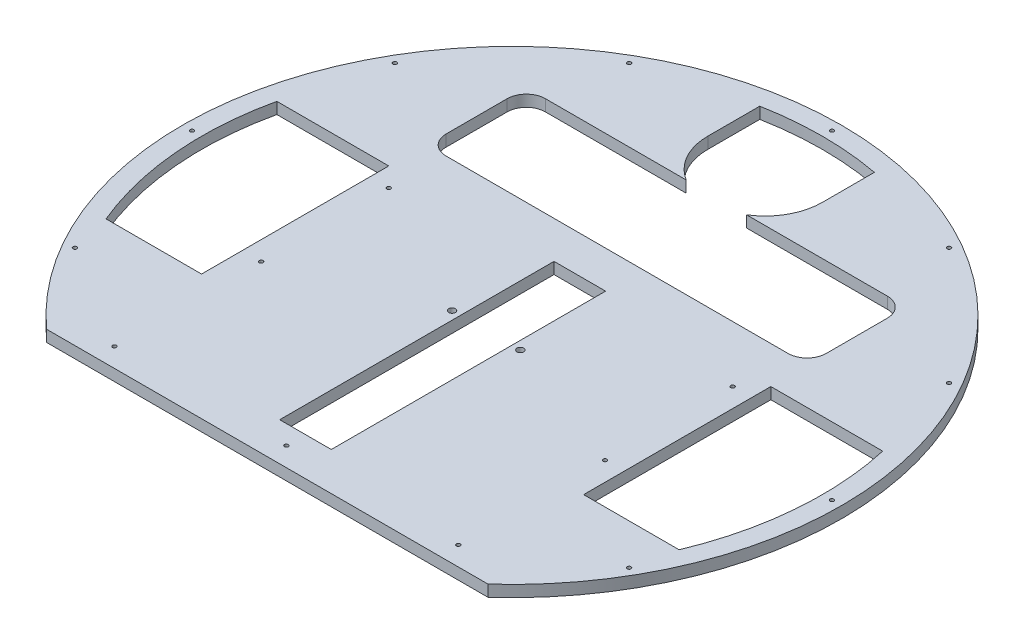
SolidWorks part; units mm, degrees
ref_plane "Front Plane" through (0, 0, 0) normal (0, 0, 1) x (1, 0, 0)
ref_plane "Top Plane" through (0, 0, 0) normal (0, 1, 0) x (1, 0, 0)
ref_plane "Right Plane" through (0, 0, 0) normal (1, 0, 0) x (0, 0, -1)
sketch "Sketch1" plane through (0, 0, 0) normal (0, 1, 0) x (1, 0, 0)
  line L0 (0, 0) -> (0, -162.5) construction
  line L2 (-100, -144.5) -> (100, -144.5)
  line L3 (-100, -144.5) -> (-100, 35.5)
  line L4 (-100, 35.5) -> (100, 35.5)
  line L5 (100, -144.5) -> (100, 35.5)
  line L6 (-100, -144.5) -> (100, 35.5) construction
  line L7 (-100, 35.5) -> (100, -144.5) construction
  circle A0 centre (0, 0) radius 162.5
  point P4 (0, -54.5)
  dimension "D1" = 325
  dimension "D2" = 180
  dimension "D3" = 35.5
  dimension "D4" = 200
sketch "Sketch2" plane through (0, 0, 0) normal (0, 1, 0) x (1, 0, 0)
  line L0 (-100, -144.5) -> (-100, 35.5) construction
  line L1 (-100, 35.5) -> (100, 35.5) construction
  line L2 (100, -144.5) -> (100, 35.5) construction
  line L3 (-100, -128.0869) -> (-100, 35.5)
  line L4 (-100, 35.5) -> (100, 35.5)
  line L5 (100, -128.0869) -> (100, 35.5)
  circle A0 centre (0, 0) radius 162.5 construction
  arc A1 (100, -128.0869) -> (-100, -128.0869) centre (0, 0) ccw
extrude "Boss-Extrude1" add sketch "Sketch2" along normal blind 6
sketch "Sketch4" plane through (0, 6, 0) normal (0, 1, 0) x (1, 0, 0)
  line L0 (0, 0) -> (0, 162.5) construction
  line L1 (119.15, -101.1581) -> (123.8764, -105.1708) construction
  line L2 (100, 35.5) -> (100, -128.0869) construction
  line L4 (-100, 35.5) -> (100, 35.5) construction
  arc A0 (100, -128.0869) -> (-100, -128.0869) centre (0, 0) ccw construction
  circle A1 centre (119.15, -101.1581) radius 1
  circle A2 centre (87.75, 86.5) radius 1
  circle A3 centre (152, 23.5891) radius 1
  circle A4 centre (-87.75, 86.5) radius 1
  circle A5 centre (99, 36.6) radius 1
  circle A6 centre (-99, 36.6) radius 1
  circle A7 centre (-152, 23.5891) radius 1
  circle A8 centre (-119.15, -101.1581) radius 1
  dimension "D1" = 2
  dimension "D3" = 6.2
  dimension "D2" = 129
  dimension "D4" = 19.15
  dimension "D5" = 52
  dimension "D6" = 51
  dimension "D7" = 87.75
  dimension "D8" = 1.1
extrude "Cut-Extrude2" [suppressed] cut sketch "Sketch4" against normal through all
sketch "Sketch5" plane through (0, 6, 0) normal (0, 1, 0) x (1, 0, 0)
  line L0 (-100, -128.0869) -> (-100, 35.5) construction
  line L1 (-100, -108.0869) -> (100, -108.0869)
  line L2 (-100, -108.0869) -> (-100, -128.0869)
  line L3 (-100, -128.0869) -> (100, -128.0869)
  line L4 (100, -108.0869) -> (100, -128.0869)
  dimension "D1" = 20
extrude "Boss-Extrude2" add sketch "Sketch5" against normal blind 6
sketch "Sketch6" plane through (0, 6, 0) normal (0, 1, 0) x (1, 0, 0)
  line L0 (0, 0) -> (0, -108.0869) construction
  line L1 (100, -108.0869) -> (-100, -108.0869) construction
  line L2 (-100, 35.5) -> (100, 35.5) construction
  line L4 (-13.5, -108.0869) -> (-13.5, 35.5)
  line L5 (-13.5, -108.0869) -> (-100, -108.0869)
  line L6 (13.5, -108.0869) -> (13.5, 35.5)
  line L7 (-13.5, -108.0869) -> (13.5, 35.5) construction
  line L8 (-13.5, 35.5) -> (13.5, -108.0869) construction
  line L9 (-100, -108.0869) -> (-100, 35.5) construction
  line L10 (-100, -108.0869) -> (-100, 35.5)
  line L11 (100, -108.0869) -> (13.5, -108.0869)
  line L12 (-13.5, 35.5) -> (-100, 35.5)
  line L13 (-100, -108.0869) -> (100, -108.0869)
  line L14 (-100, 35.5) -> (-100, -108.0869)
  line L15 (100, 35.5) -> (-100, 35.5)
  line L16 (100, -108.0869) -> (100, 35.5)
  line L17 (-100, -108.0869) -> (-13.5, -108.0869)
  line L18 (-100, 35.5) -> (-100, -108.0869)
  line L19 (100, 35.5) -> (13.5, 35.5)
  line L20 (100, -108.0869) -> (100, 35.5)
  line L21 (13.5, -108.0869) -> (100, -108.0869)
  point P5 (0, -36.2934)
  line M5 (100, -108.0869) -> (-100, -108.0869)
  line M6 (-100, -108.0869) -> (-100, 35.5)
  line M7 (-100, 35.5) -> (100, 35.5)
  line M8 (100, 35.5) -> (100, -108.0869)
  dimension "D1" = 27
  dimension "D2" = 0
extrude "Boss-Extrude3" add sketch "Sketch6" against normal through all contours L4 M5 M7 M6 | L6 M5 M8 M7 region at (-56.75, 6, 36.2934) region at (56.75, 6, 36.2934)
sketch "Sketch7" plane through (0, 6, 0) normal (0, 1, 0) x (1, 0, 0)
  line L0 (-150, -62.5) -> (-100, -62.5)
  line L1 (-100, -144.5) -> (-100, 35.5) construction
  line L2 (-158.5749, 35.5) -> (-100, 35.5)
  line L3 (-100, 35.5) -> (-100, -62.5)
  line L4 (0, 0) -> (0, -162.5) construction
  line L5 (100, 35.5) -> (100, -62.5)
  line L6 (158.5749, 35.5) -> (100, 35.5)
  line L7 (150, -62.5) -> (100, -62.5)
  line L8 (-100, 35.5) -> (100, 35.5) construction
  arc A0 (100, -128.0869) -> (-100, -128.0869) centre (0, 0) ccw construction
  circle A1 centre (0, 0) radius 162.5 construction
  arc A2 (-158.5749, 35.5) -> (-150, -62.5) centre (0, 0) ccw
  arc A3 (158.5749, 35.5) -> (150, -62.5) centre (0, 0) cw
  dimension "D1" = 50
extrude "Cut-Extrude3" cut sketch "Sketch7" against normal through all
sketch "Sketch8" plane through (0, 6, 0) normal (0, 1, 0) x (1, 0, 0)
  line L0 (0, 162.5) -> (0, 0) construction
  line L1 (-30, 132.5) -> (-30, 159.7068)
  line L2 (30, 132.5) -> (30, 159.7068)
  arc A0 (-30, 132.5) -> (30, 132.5) centre (0, 132.5) ccw
  circle A1 centre (0, 0) radius 162.5 construction
  arc A2 (30, 159.7068) -> (-30, 159.7068) centre (0, 0) ccw
  dimension "D1" = 60
extrude "Cut-Extrude4" cut sketch "Sketch8" against normal through all
sketch "Sketch9" plane through (0, 6, 0) normal (0, 1, 0) x (1, 0, 0)
  line L0 (0, 0) -> (0, 162.5) construction
  line L1 (-99.5, 107) -> (99.5, 107)
  line L2 (-99.5, 107) -> (-99.5, 55)
  line L3 (-99.5, 55) -> (99.5, 55)
  line L4 (99.5, 107) -> (99.5, 55)
  line L5 (-99.5, 107) -> (99.5, 55) construction
  line L6 (-99.5, 55) -> (99.5, 107) construction
  line L7 (-100, 35.5) -> (100, 35.5) construction
  circle A0 centre (0, 0) radius 162.5 construction
  point P0 (0, 81)
  dimension "D1" = 52
  dimension "D2" = 199
  dimension "D3" = 19.5
extrude "Cut-Extrude5" cut sketch "Sketch9" against normal through all
sketch "Sketch10" plane through (0, 6, 0) normal (0, 1, 0) x (1, 0, 0)
  line L0 (-100, -128.0869) -> (-115.5422, -128.0869)
  line L1 (100, -128.0869) -> (115.5422, -128.0869)
  arc A0 (115.5422, -128.0869) -> (-115.5422, -128.0869) centre (0, 0) ccw
  circle A1 centre (0, 0) radius 162.5 construction
  arc A2 (100, -128.0869) -> (-100, -128.0869) centre (0, 0) ccw
  dimension "D1" = 10
extrude "Boss-Extrude4" add sketch "Sketch10" against normal through all
fillet "Fillet1" radius 10 4 edges at (99.5, 3, -107) (99.5, 3, -55) (-99.5, 3, -55) (-99.5, 3, -107)
sketch "Sketch11" plane through (0, 6, 0) normal (0, 1, 0) x (1, 0, 0)
  line L0 (0, 172.5) -> (0, 162.5) construction
  arc A1 (115.5422, -128.0869) -> (-115.5422, -128.0869) centre (0, 0) ccw construction
  arc A2 (30, 159.7068) -> (-30, 159.7068) centre (0, 0) ccw construction
  circle A3 centre (0, 167.5) radius 1
  circle A4 centre (83.75, 145.0593) radius 1
  circle A5 centre (145.0593, 83.75) radius 1
  circle A6 centre (167.5, 0) radius 1
  circle A7 centre (145.0593, -83.75) radius 1
  circle A8 centre (83.75, -145.0593) radius 1
  circle A9 centre (0, -167.5) radius 1
  circle A10 centre (-83.75, -145.0593) radius 1
  circle A11 centre (-145.0593, -83.75) radius 1
  circle A12 centre (-167.5, 0) radius 1
  circle A13 centre (-145.0593, 83.75) radius 1
  circle A14 centre (-83.75, 145.0593) radius 1
  point P36 (0, 0)
  dimension "D1" = 2
  dimension "D2" = 12
extrude "Cut-Extrude6" cut sketch "Sketch11" against normal through all
sketch "Sketch12" plane through (0, 6, 0) normal (0, 1, 0) x (1, 0, 0)
  line L0 (-125.7447, -118.0869) -> (125.7447, -118.0869) construction
  line L1 (-115.5422, -128.0869) -> (115.5422, -128.0869) construction
  line L2 (-100, -144.5) -> (-100, 35.5) construction
  line L3 (100, -144.5) -> (100, 35.5) construction
  line L4 (-90, -118.0869) -> (-90, 35.5) construction
  line L5 (0, 0) -> (0, -118.0869) construction
  line L6 (-100, 35.5) -> (100, 35.5) construction
  arc A0 (115.5422, -128.0869) -> (-115.5422, -128.0869) centre (0, 0) ccw construction
  circle A1 centre (0, -118.0869) radius 1
  circle A2 centre (-90, -118.0869) radius 1
  circle A3 centre (90, -118.0869) radius 1
  circle A4 centre (-90, 25.5) radius 1
  circle A5 centre (-90, -41.2934) radius 1
  circle A6 centre (90, -41.2934) radius 1
  circle A7 centre (90, 25.5) radius 1
  dimension "D2" = 2
  dimension "D1" = 10
  dimension "D3" = 10
  dimension "D4" = 10
  dimension "D5" = 10
extrude "Cut-Extrude7" cut sketch "Sketch12" against normal through all
sketch "Sketch13" plane through (0, 6, 0) normal (0, 1, 0) x (1, 0, 0)
  line L0 (0, 0) -> (0, 35.5) construction
  line L1 (-13.5, 35.5) -> (13.5, 35.5) construction
  circle A0 centre (-17.875, -13.5) radius 1.75
  circle A1 centre (17.875, -13.5) radius 1.75
  dimension "D3" = 3.5
  dimension "D1" = 35.75
  dimension "D2" = 13.5
extrude "Cut-Extrude8" cut sketch "Sketch13" against normal blind 10
